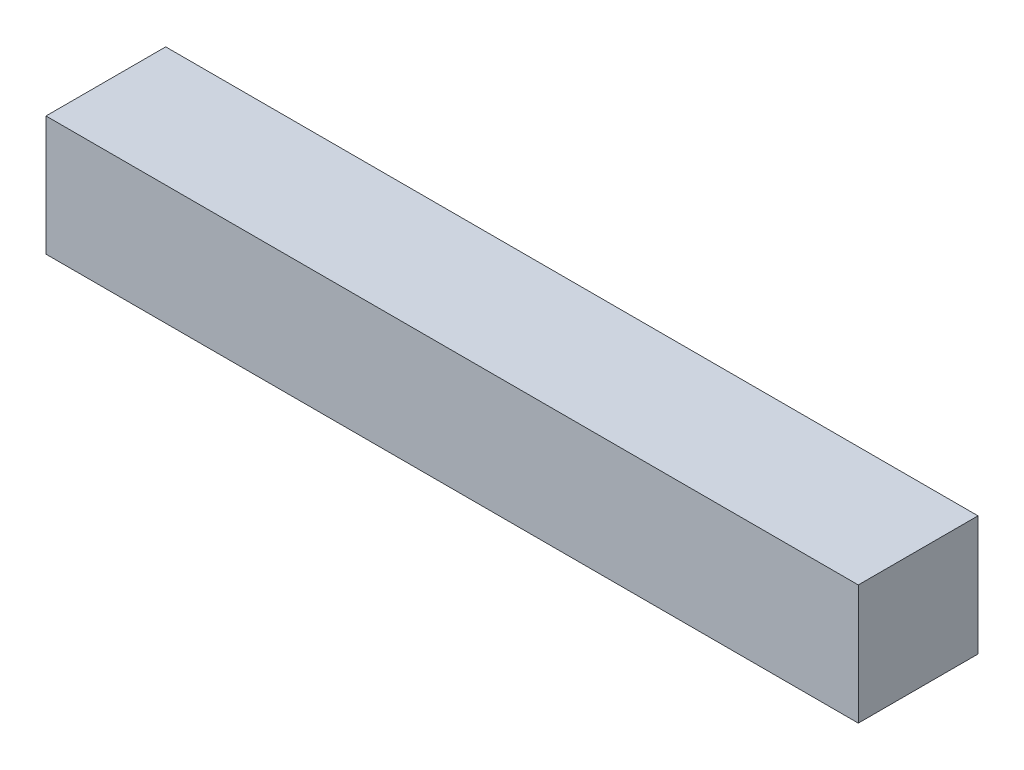
SolidWorks part; units mm, degrees
material "Oak"
ref_plane "Alzado" through (0, 0, 0) normal (0, 0, 1) x (1, 0, 0)
ref_plane "Planta" through (0, 0, 0) normal (0, 1, 0) x (1, 0, 0)
ref_plane "Vista lateral" through (0, 0, 0) normal (1, 0, 0) x (0, 0, -1)
sketch "Sketch1" plane through (0, 0, 0) normal (1, 0, 0) x (0, 0, -1)
  line L0 (-7, 7) -> (7, -7) construction
  line L1 (-7, 7) -> (7, 7)
  line L2 (-7, 7) -> (-7, -7)
  line L3 (-7, -7) -> (7, -7)
  line L4 (7, 7) -> (7, -7)
  dimension "D1" = 14
extrude "Boss-Extrude1" add sketch "Sketch1" along normal blind 95
